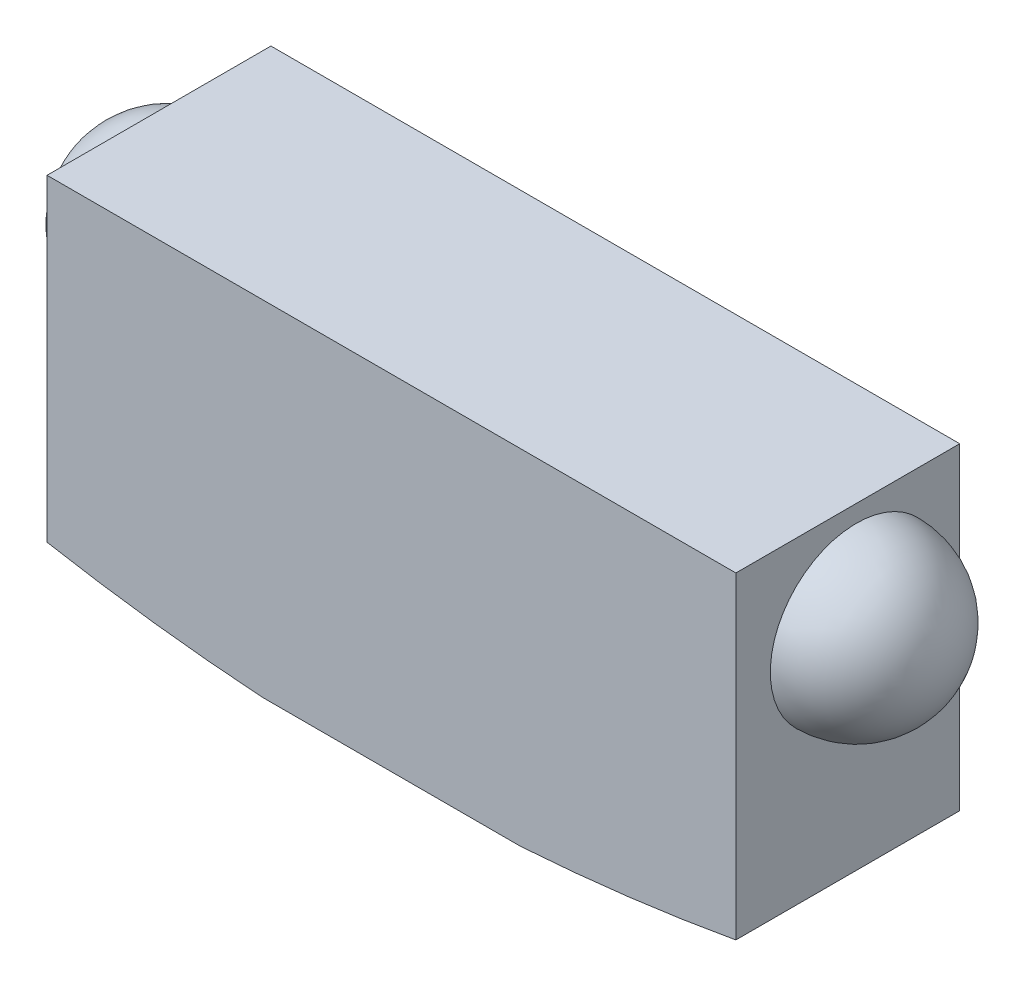
SolidWorks part; units mm, degrees
ref_plane "Front Plane" through (0, 0, 0) normal (0, 0, 1) x (1, 0, 0)
ref_plane "Top Plane" through (0, 0, 0) normal (0, 1, 0) x (1, 0, 0)
ref_plane "Right Plane" through (0, 0, 0) normal (1, 0, 0) x (0, 0, -1)
sketch "Sketch2" plane through (0, 0, 0) normal (0, 1, 0) x (1, 0, 0)
  line L1 (-100, -65) -> (100, -65)
  line L2 (-100, -65) -> (-100, 65)
  line L3 (-100, 65) -> (100, 65)
  line L4 (100, -65) -> (100, 65)
  line L5 (-100, -65) -> (100, 65) construction
  line L6 (-100, 65) -> (100, -65) construction
  point P0 (0, 0)
  dimension "D1" = 130
  dimension "D2" = 200
extrude "Boss-Extrude1" add sketch "Sketch2" along normal blind 50 and the other way blind 50
sketch "Sketch4" plane through (0, 0, 65) normal (0, 0, 1) x (1, 0, 0)
  circle A0 centre (0, 0) radius 5
extrude "Boss-Extrude2" add sketch "Sketch4" along normal blind 20
sketch "Sketch6" plane through (-100, 0, 0) normal (-1, 0, 0) x (0, 0, 1)
  line L3 (-35, -5) -> (-35, 45)
  arc A1 (-35, 45) -> (-35, -5) centre (-35, 20) cw
  dimension "D1" = 50
  dimension "D2" = 25
revolve "Revolve1" add sketch "Sketch6" angle 360 about L3
mirror "Mirror1" about plane through (0, 0, 0) normal (1, 0, 0) of "Revolve1"
sketch "Sketch7" plane through (0, 0, -65) normal (0, 0, -1) x (-1, 0, 0)
  line L0 (-100, -42.2859) -> (100, -42.2859)
  line L1 (-100, -50) -> (-100, 50) construction
  line L2 (100, -50) -> (100, 50) construction
  line L3 (-100, -42.2859) -> (-100, -50)
  line L5 (-100, -42.2859) -> (100, -42.2859)
  line L6 (-100, -42.2859) -> (-100, -50)
  line L7 (-100, -50) -> (100, -50)
  line L8 (100, -42.2859) -> (100, -50)
  arc A0 (-100, -42.2859) -> (100, -42.2859) centre (0, 510.776) ccw
  line M5 (100, -50) -> (100, 50)
  line M7 (-100, 50) -> (-100, -50)
  line M8 (-100, -50) -> (100, -50)
extrude "Cut-Extrude1" cut sketch "Sketch7" against normal blind 142 contours A0 M7 M8 | A0 M8 M5 region at (81.0559, -47.5985, -65) region at (-81.0559, -47.5985, -65)
sketch "Sketch8" plane through (0, 50, 0) normal (0, 1, 0) x (1, 0, 0)
  line L0 (-100, 65) -> (-100, -65) construction
  line L1 (-100, 0) -> (100.1471, 0)
  line L2 (-100, 0) -> (-100, -101.7292)
  line L3 (-100, -101.7292) -> (100.1471, -101.7292)
  line L4 (100.1471, 0) -> (100.1471, -101.7292)
extrude "Cut-Extrude2" cut sketch "Sketch8" against normal blind 142
